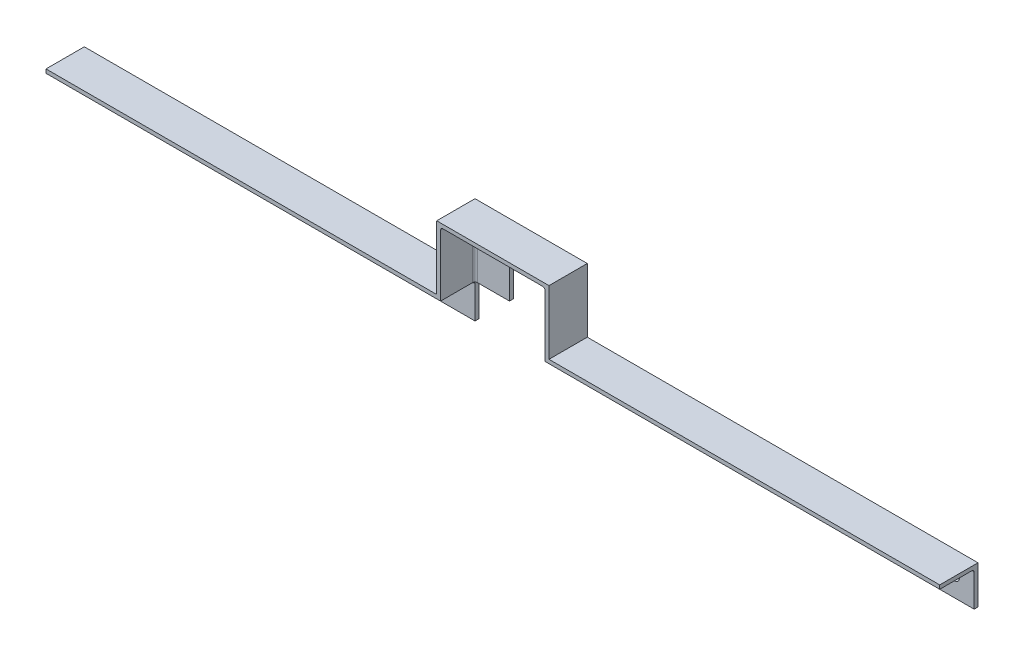
SolidWorks part; units mm, degrees
ref_plane "Plan de face" through (0, 0, 0) normal (0, 0, 1) x (1, 0, 0)
ref_plane "Plan de dessus" through (0, 0, 0) normal (0, 1, 0) x (1, 0, 0)
ref_plane "Plan de droite" through (0, 0, 0) normal (1, 0, 0) x (0, 0, -1)
ref_plane "Plan1" through (-178.4106, 149.3059, -1.5) normal (-1, 0, 0) x (0, 0, 1)
sketch "Esquisse2" plane through (0, 0, 1.5) normal (0, 0, 1) x (1, 0, 0)
  line L0 (-25.3924, 124.3059) -> (-178.4106, 124.3059)
  line L1 (-178.4106, 124.3059) -> (-178.4106, 149.3059)
  line L2 (-178.4106, 149.3059) -> (-222.3743, 149.3059)
  line L3 (-222.3743, 149.3059) -> (-222.3743, 124.3059)
  line L4 (-222.3743, 124.3059) -> (-375.3924, 124.3059)
  line L5 (-375.3924, 124.3059) -> (-375.3924, 109.3059)
  line L6 (-375.3924, 124.3059) -> (-375.3924, -75.6941) construction
  line L7 (-375.3924, 109.3059) -> (-207.3743, 109.3059)
  line L8 (-207.3743, 109.3059) -> (-207.3743, 134.3059)
  line L10 (-207.3743, 134.3059) -> (-193.4106, 134.3059)
  line L11 (-193.4106, 134.3059) -> (-193.4106, 109.3059)
  line L12 (-193.4106, 109.3059) -> (-25.3924, 109.3059)
  line L14 (-25.3924, -75.6941) -> (-25.3924, 124.3059) construction
  line L15 (-25.3924, 109.3059) -> (-25.3924, 124.3059)
  dimension "D1" = 15
  dimension "D2" = 15
  dimension "D3" = 15
  dimension "D4" = 15
extrude "Boss.-Extru.1" add sketch "Esquisse2" along normal blind 1.5
sketch "Esquisse3" plane through (0, 0, 3) normal (0, 0, 1) x (1, 0, 0)
  line L0 (-375.3924, 122.8059) -> (-220.8743, 122.8059)
  line L1 (-375.3924, 124.3059) -> (-375.3924, 109.3059) construction
  line L2 (-220.8743, 122.8059) -> (-220.8743, 147.8059)
  line L3 (-220.8743, 147.8059) -> (-179.9106, 147.8059)
  line L4 (-179.9106, 147.8059) -> (-179.9106, 122.8059)
  line L5 (-179.9106, 122.8059) -> (-25.3924, 122.8059)
  line L6 (-25.3924, 109.3059) -> (-25.3924, 124.3059) construction
  line L7 (-25.3924, 122.8059) -> (-25.3924, 124.3059)
  line L8 (-25.3924, 124.3059) -> (-178.4106, 124.3059)
  line L9 (-178.4106, 124.3059) -> (-178.4106, 149.3059)
  line L10 (-178.4106, 149.3059) -> (-222.3743, 149.3059)
  line L11 (-222.3743, 149.3059) -> (-222.3743, 124.3059)
  line L12 (-222.3743, 124.3059) -> (-375.3924, 124.3059)
  line L13 (-375.3924, 124.3059) -> (-375.3924, 122.8059)
  dimension "D1" = 1.5
  dimension "D2" = 1.5
  dimension "D3" = 1.5
  dimension "D4" = 1.5
  dimension "D5" = 1.5
extrude "Boss.-Extru.2" add sketch "Esquisse3" along normal blind 13.5
hole_wizard "Dégagement M32" positions "Esquisse3D1" profile "Esquisse6" hole size "M3" standard "ISO"
sketch3d "Esquisse3D1"
  line L0 (-375.3924, 109.3059, 3) -> (-207.3743, 109.3059, 3) construction
  line L1 (-375.3924, 122.8059, 3) -> (-375.3924, 109.3059, 3) construction
  line L3 (-193.4106, 109.3059, 3) -> (-25.3924, 109.3059, 3) construction
  line L4 (-25.3924, 109.3059, 3) -> (-25.3924, 122.8059, 3) construction
  line L6 (-179.9106, 147.8059, 3) -> (-179.9106, 122.8059, 3) construction
  line L7 (-220.8743, 122.8059, 3) -> (-220.8743, 147.8059, 3) construction
  point P0 (-229.8743, 116.8059, 3)
  point P2 (-300.3924, 116.8059, 3)
  point P4 (-367.8924, 116.8059, 3)
  point P13 (-170.9106, 116.8059, 3)
  point P15 (-100.3924, 116.8059, 3)
  point P17 (-32.8924, 116.8059, 3)
  dimension "D1" = 7.5
  dimension "D2" = 7.5
  dimension "D3" = 7.5
  dimension "D4" = 7.5
  dimension "D5" = 75
  dimension "D6" = 9
  dimension "D7" = 7.5
  dimension "D11" = 9
  dimension "D8" = 7.5
  dimension "D9" = 7.5
  dimension "D10" = 75
  dimension "D12" = 7.5
sketch "Esquisse6" plane through (-229.8743, 116.8059, 3) normal (1, 0, 0) x (0, -1, 0)
  line L0 (0, 0) -> (0, 11.0215)
  line L1 (0, 11.0215) -> (1.7, 10)
  line L2 (1.7, 10) -> (1.7, 0)
  line L5 (1.7, 0) -> (0, 0)
  line L10 (0, 11.0215) -> (-1.7, 10) construction
  line L11 (0, -6.35) -> (0, 107.95) construction
  dimension "Diamètre du perçage" = 3.4
  dimension "Profondeur du perçage" = 10
  dimension "Angle de pointe" = 118
hole_wizard "Dégagement M31" positions "Esquisse3D2" profile "Esquisse7" hole size "M3" standard "ISO"
sketch3d "Esquisse3D2"
  line L0 (-193.4106, 134.3059, 3) -> (-193.4106, 109.3059, 3) construction
  line L1 (-207.3743, 109.3059, 3) -> (-207.3743, 134.3059, 3) construction
  line L6 (-207.3743, 134.3059, 3) -> (-193.4106, 134.3059, 3) construction
  point P0 (-214.8743, 137.3059, 3)
  point P2 (-185.9106, 137.3059, 3)
  dimension "D1" = 7.5
  dimension "D2" = 7.5
  dimension "D3" = 3
  dimension "D4" = 3
sketch "Esquisse7" plane through (-214.8743, 137.3059, 3) normal (1, 0, 0) x (0, -1, 0)
  line L0 (0, 0) -> (0, 11.0215)
  line L1 (0, 11.0215) -> (1.7, 10)
  line L2 (1.7, 10) -> (1.7, 0)
  line L5 (1.7, 0) -> (0, 0)
  line L10 (0, 11.0215) -> (-1.7, 10) construction
  line L11 (0, -6.35) -> (0, 107.95) construction
  dimension "Diamètre du perçage" = 3.4
  dimension "Profondeur du perçage" = 10
  dimension "Angle de pointe" = 118
sketch "Esquisse12" plane through (0, 0, 3) normal (0, 0, 1) x (1, 0, 0)
  line L1 (-207.3743, 109.3059) -> (-220.8743, 109.3059)
  line L2 (-207.3743, 109.3059) -> (-207.3743, 122.8059)
  line L3 (-207.3743, 122.8059) -> (-220.8743, 122.8059)
  line L4 (-220.8743, 109.3059) -> (-220.8743, 122.8059)
  line L5 (-193.4106, 109.3059) -> (-179.9106, 109.3059)
  line L6 (-193.4106, 109.3059) -> (-193.4106, 122.8059)
  line L7 (-193.4106, 122.8059) -> (-179.9106, 122.8059)
  line L8 (-179.9106, 109.3059) -> (-179.9106, 122.8059)
extrude "Enlèv. mat.-Extru.1" cut sketch "Esquisse12" against normal blind 1.5
fillet "Congé1" radius 1 3 edges at (-200.3924, 147.8059, 3)
fillet "Congé2" radius 1 6 edges at (-220.8743, 147.8059, 10.25) (-220.8743, 147.513, 3.2929) (-179.9106, 147.8059, 10.25) (-179.9106, 147.513, 3.2929) (-220.8743, 134.8059, 3) (-179.9106, 134.8059, 3)
